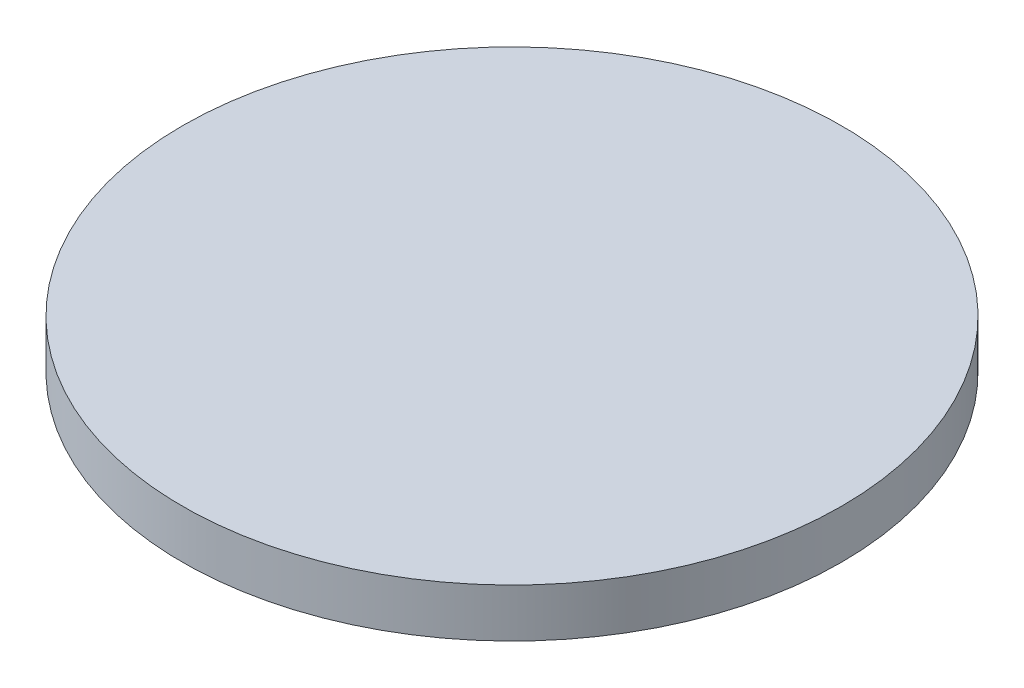
SolidWorks part; units mm, degrees
material "Glass"
ref_plane "Front Plane" through (0, 0, 0) normal (0, 0, 1) x (1, 0, 0)
ref_plane "Top Plane" through (0, 0, 0) normal (0, 1, 0) x (1, 0, 0)
ref_plane "Right Plane" through (0, 0, 0) normal (1, 0, 0) x (0, 0, -1)
sketch "Sketch1" plane through (0, 0, 0) normal (0, 0, 1) x (1, 0, 0)
  line L0 (-55.2, -0.2) -> (-52.5, -0.2)
  line L1 (0, 0) -> (-55, 0)
  line L2 (0, 0) -> (0, 8.1)
  line L3 (0, 8.1) -> (-55, 8.1)
  line L4 (-55, 0) -> (-55, 8.1)
  line L5 (-52.5, -0.2) -> (-52.5, -3.2)
  line L6 (-52.5, -3.2) -> (-63.2, -3.2)
  line L7 (-63.2, -3.2) -> (-63.2, 11.8)
  line L12 (-55.2, 11.8) -> (-55.2, -0.2)
  line L13 (-55.2, 11.8) -> (-63.2, 11.8)
  line L14 (0, 0) -> (0, 30.013) construction
sketch "Sketch3" plane through (0, 0, 0) normal (0, 0, 1) x (1, 0, 0)
  line L0 (0, 0) -> (0, 30.013) construction
  line L1 (0, 0) -> (0, 8.1) construction
  line L2 (0, 0) -> (-55, 0) construction
  line L3 (-55, 0) -> (-55, 8.1) construction
  line L4 (0, 8.1) -> (-55, 8.1) construction
  line L5 (0, 0) -> (0, 30.013) construction
  line L6 (0, 0) -> (0, 8.1)
  line L7 (0, 0) -> (-55, 0)
  line L8 (-55, 0) -> (-55, 8.1)
  line L9 (0, 8.1) -> (-55, 8.1)
revolve "Filter" add sketch "Sketch3" angle 360 about L5 region at (-27.5, 4.05, 0)
